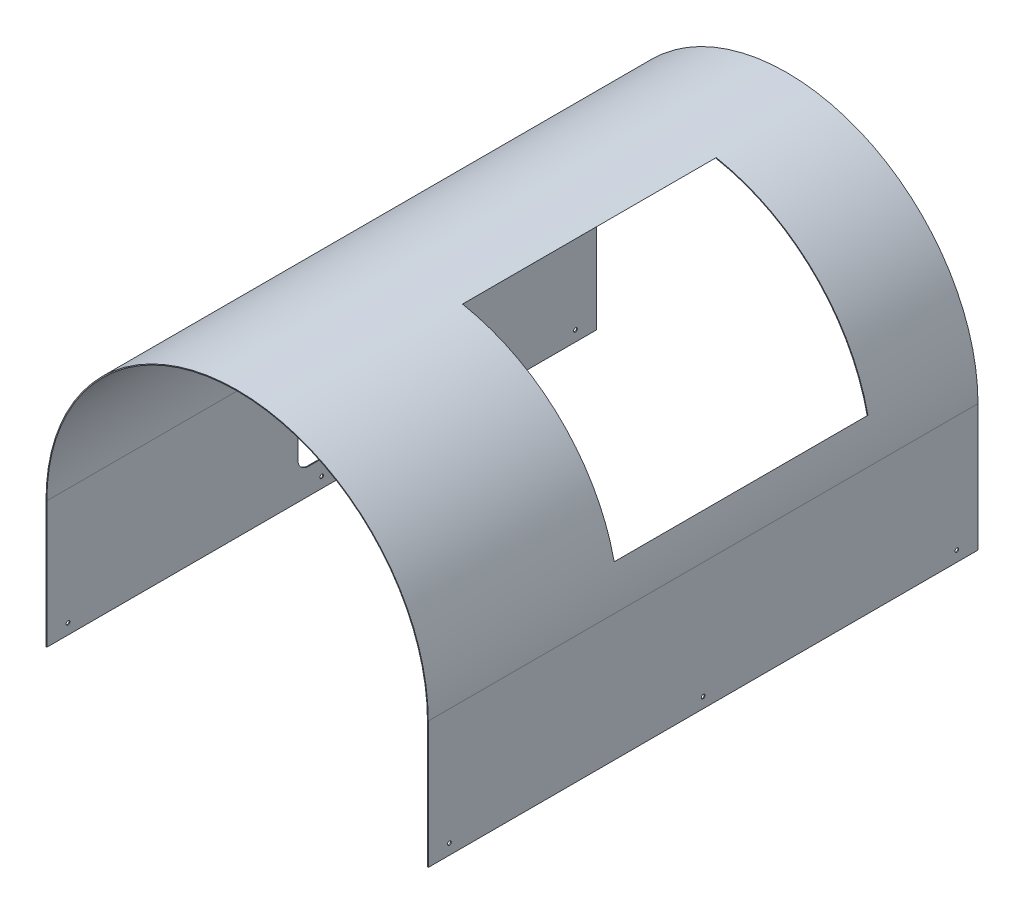
SolidWorks part; units mm, degrees
ref_plane "Front Plane" through (0, 0, 0) normal (0, 0, 1) x (1, 0, 0)
ref_plane "Top Plane" through (0, 0, 0) normal (0, 1, 0) x (1, 0, 0)
ref_plane "Right Plane" through (0, 0, 0) normal (1, 0, 0) x (0, 0, -1)
sketch "Sketch1" plane through (0, 0, 0) normal (0, 0, 1) x (1, 0, 0)
  line L0 (-228.6, -36.83) -> (-228.6, -189.23)
  line L1 (-228.6, -189.23) -> (230.632, -189.23)
  line L2 (-228.6, -189.23) -> (-228.6, 192.786) construction
  line L3 (-228.6, 192.786) -> (230.632, 192.786) construction
  line L4 (230.632, -189.23) -> (230.632, 192.786) construction
  line L5 (230.632, -36.83) -> (230.632, -189.23)
  circle A0 centre (0, 0) radius 127 construction
  arc A2 (230.632, -36.83) -> (-228.6, -36.83) centre (1.016, -36.83) ccw
  dimension "D1" = 254
  dimension "D4" = 189.23
  dimension "D5" = 228.6
  dimension "D2" = 459.232
  dimension "D3" = 382.016
extrude "Boss-Extrude1" add sketch "Sketch1" along normal blind 660.4
sketch "Sketch2" plane through (0, 0, 660.4) normal (0, 0, 1) x (1, 0, 0)
  line L0 (-228.6, -189.23) -> (230.632, -189.23) construction
  line L2 (-227.584, -36.83) -> (-227.584, -189.23)
  line L3 (-227.584, -189.23) -> (229.616, -189.23)
  line L4 (229.616, -36.83) -> (229.616, -189.23)
  line L5 (-187.6415, 88.9417) -> (229.616, -189.23) construction
  line L6 (-227.584, -189.23) -> (189.6735, 88.9417) construction
  arc A1 (229.616, -36.83) -> (-227.584, -36.83) centre (1.016, -36.83) ccw
  dimension "D2" = 457.2
extrude "Cut-Extrude1" cut sketch "Sketch2" against normal blind 660.4
ref_plane "Plane1" through (96.3898, 96.8182, 0) normal (0.7055, 0.7087, 0) x (0.7087, -0.7055, 0)
sketch "Sketch3" plane through (96.3898, 96.8182, 0) normal (0.7055, 0.7087, 0) x (0.7087, -0.7055, 0)
  line L0 (189.4276, -660.4) -> (189.4276, 0) construction
  line L1 (-102.6724, -127) -> (151.3276, -127)
  line L2 (-102.6724, -127) -> (-102.6724, -431.8)
  line L3 (-102.6724, -431.8) -> (151.3276, -431.8)
  line L4 (151.3276, -127) -> (151.3276, -431.8)
  line L5 (-102.6724, -127) -> (151.3276, -431.8) construction
  line L6 (-102.6724, -431.8) -> (151.3276, -127) construction
  line L7 (189.4276, 0) -> (-202.9111, 0) construction
  point P0 (24.3276, -279.4)
  dimension "D1" = 304.8
  dimension "D2" = 254
  dimension "D3" = 38.1
  dimension "D4" = 127
extrude "Cut-Extrude2" cut sketch "Sketch3" along normal blind 152.4
ref_plane "Plane2" through (-95.3783, 95.8022, 0) normal (0.7055, -0.7087, 0) x (-0.7087, -0.7055, 0)
sketch "Sketch4" plane through (-228.6, 0, 0) normal (-1, 0, 0) x (0, 0, 1)
  line L1 (183.515, -65.405) -> (346.075, -65.405)
  line L2 (170.815, -78.105) -> (170.815, -145.415)
  line L3 (183.515, -158.115) -> (346.075, -158.115)
  line L4 (358.775, -78.105) -> (358.775, -145.415)
  line L5 (0, -36.83) -> (0, -189.23) construction
  line L6 (660.4, -36.83) -> (0, -36.83) construction
  arc A0 (170.815, -78.105) -> (183.515, -65.405) centre (183.515, -78.105) cw
  arc A1 (183.515, -158.115) -> (170.815, -145.415) centre (183.515, -145.415) cw
  arc A2 (358.775, -145.415) -> (346.075, -158.115) centre (346.075, -145.415) cw
  arc A3 (358.775, -78.105) -> (346.075, -65.405) centre (346.075, -78.105) ccw
  point P11 (170.815, -65.405)
  point P14 (170.815, -158.115)
  point P17 (358.775, -158.115)
  dimension "D4" = 12.7
  dimension "D5" = 12.7
  dimension "D1" = 92.71
  dimension "D2" = 170.815
  dimension "D3" = 187.96
  dimension "D6" = 28.575
extrude "Cut-Extrude3" cut sketch "Sketch4" against normal blind 2.54
sketch "Sketch5" plane through (-228.6, 0, 0) normal (-1, 0, 0) x (0, 0, 1)
  line L0 (0, -176.53) -> (660.4, -176.53) construction
  line L1 (0, -36.83) -> (0, -189.23) construction
  line L2 (660.4, -36.83) -> (660.4, -189.23) construction
  line L3 (660.4, -189.23) -> (0, -189.23) construction
  point P8 (25.4, -176.53)
  point P9 (330.2, -176.53)
  point P10 (635, -176.53)
  dimension "D1" = 12.7
  dimension "D2" = 25.4
  dimension "D3" = 25.4
sketch "Sketch6" plane through (230.632, 0, 0) normal (1, 0, 0) x (0, 0, -1)
  line L0 (-660.4, -176.53) -> (0, -176.53) construction
  line L1 (-660.4, -189.23) -> (-660.4, -36.83) construction
  line L2 (0, -189.23) -> (0, -36.83) construction
  line L3 (-660.4, -189.23) -> (0, -189.23) construction
  point P8 (-330.2, -176.53)
  point P9 (-635, -176.53)
  point P10 (-25.4, -176.53)
  dimension "D1" = 12.7
  dimension "D2" = 25.4
  dimension "D3" = 25.4
hole_wizard "#8 Clearance Hole1" positions "Sketch8" profile "Sketch9" hole size "#8" standard "ANSI Inch" end condition through all
sketch "Sketch8" plane through (230.632, 0, 0) normal (1, 0, 0) x (0, 0, -1)
  point P0 (-635, -176.53)
  point P3 (-330.2, -176.53)
  point P6 (-25.4, -176.53)
sketch "Sketch9" plane through (230.632, -176.53, 635) normal (0, 1, 0) x (0, 0, -1)
  line L0 (0, 0) -> (0, 459.232)
  line L1 (0, 459.232) -> (2.2479, 459.232)
  line L2 (2.2479, 459.232) -> (2.2479, 0)
  line L5 (2.2479, 0) -> (0, 0)
  line L11 (0, -6.35) -> (0, 107.95) construction
  dimension "Thru Hole Dia." = 4.4958
  dimension "Thru Hole Depth" = 459.232
sketch "Sketch13" plane through (0, -189.23, 0) normal (0, -1, 0) x (1, 0, 0)
  line L0 (1.016, 660.4) -> (1.016, 0) construction
  line L1 (-228.6, 660.4) -> (230.632, 660.4) construction
  line L2 (-228.6, 660.4) -> (-228.6, 0) construction
  line L3 (-228.6, 0) -> (230.632, 0) construction
  line L4 (230.632, 660.4) -> (230.632, 0) construction
  point P8 (1.016, 635)
  point P10 (1.016, 266.7)
  point P11 (1.016, 25.4)
  dimension "D1" = 25.4
  dimension "D2" = 266.7
